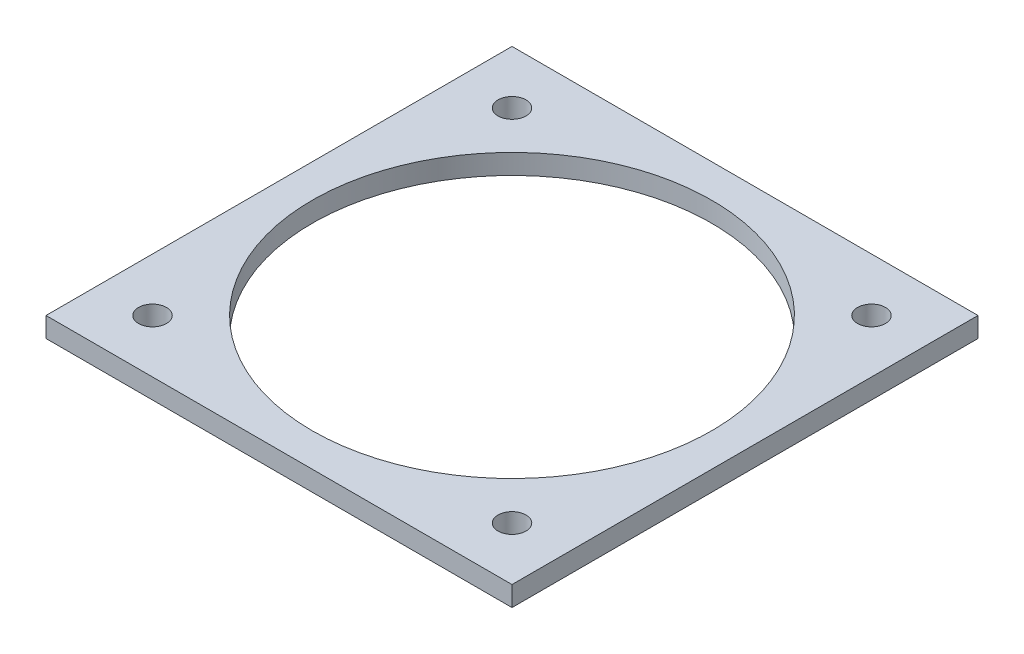
SolidWorks part; units mm, degrees
material "6061-T6 (SS)"
ref_plane "前视基准面" through (0, 0, 0) normal (0, 0, 1) x (1, 0, 0)
ref_plane "上视基准面" through (0, 0, 0) normal (0, 1, 0) x (1, 0, 0)
ref_plane "右视基准面" through (0, 0, 0) normal (1, 0, 0) x (0, 0, -1)
sketch "草图1" plane through (0, 0, 0) normal (0, 1, 0) x (1, 0, 0)
  line L1 (-35, -35) -> (35, -35)
  line L2 (-35, -35) -> (-35, 35)
  line L3 (-35, 35) -> (35, 35)
  line L4 (35, -35) -> (35, 35)
  line L5 (-35, -35) -> (35, 35) construction
  line L6 (-35, 35) -> (35, -35) construction
  circle A0 centre (0, 0) radius 30
  point P0 (0, 0)
  dimension "D3" = 60
  dimension "D1" = 70
  dimension "D2" = 70
extrude "凸台-拉伸1" add sketch "草图1" along normal blind 3
sketch "草图2" plane through (0, 3, 0) normal (0, 1, 0) x (1, 0, 0)
  line L0 (-35, -35) -> (35, 35) construction
  line L1 (35, 35) -> (-35, 35) construction
  circle A0 centre (27, 27) radius 2.1
  dimension "D1" = 4.2
  dimension "D2" = 8
extrude "切除-拉伸1" cut sketch "草图2" against normal blind 10
pattern_circular "阵列(圆周)1" count 4 over 360 about axis through (0, 3, 0) along (0, -1, 0) of "切除-拉伸1"
